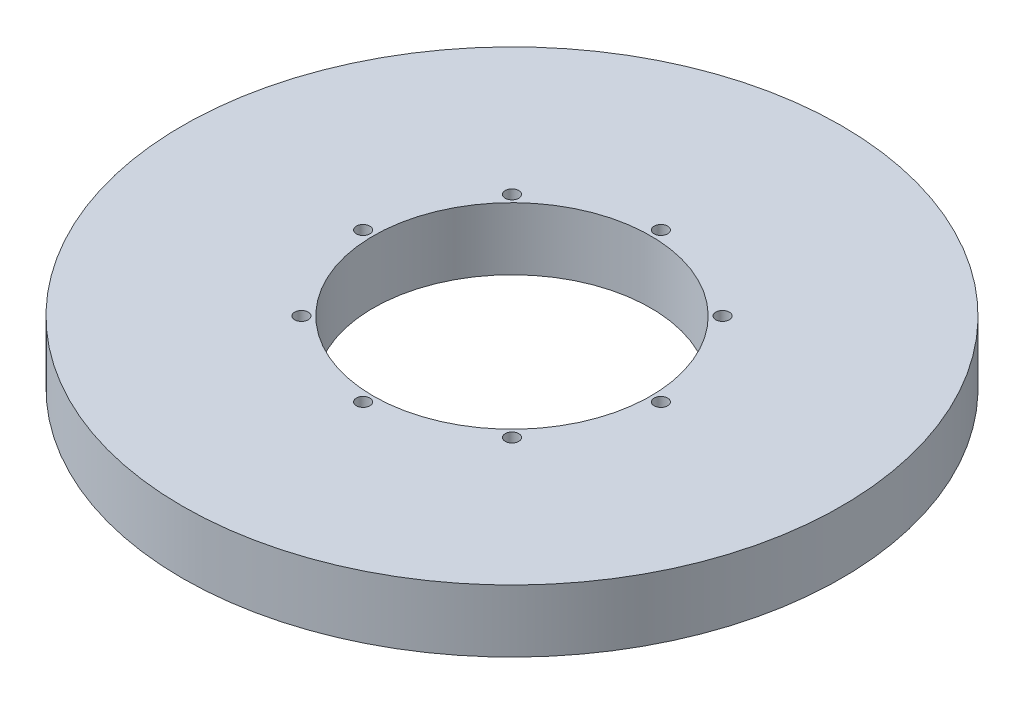
SolidWorks part; units mm, degrees
ref_plane "Front Plane" through (0, 0, 0) normal (0, 0, 1) x (1, 0, 0)
ref_plane "Top Plane" through (0, 0, 0) normal (0, 1, 0) x (1, 0, 0)
ref_plane "Right Plane" through (0, 0, 0) normal (1, 0, 0) x (0, 0, -1)
sketch "Sketch1" plane through (0, 0, 0) normal (0, 1, 0) x (1, 0, 0)
  circle A0 centre (0, 0) radius 95
  dimension "FLANGE_OD" = 190
extrude "Boss-Extrude1" add sketch "Sketch1" along normal blind 18
sketch "Sketch2" plane through (0, 0, 0) normal (0, 1, 0) x (1, 0, 0)
  circle A0 centre (0, 0) radius 40
  dimension "BORE_D" = 80
extrude "Cut-Extrude1" cut sketch "Sketch2" along normal through all
sketch "Sketch3" plane through (0, 18, 0) normal (0, 1, 0) x (1, 0, 0)
  circle A0 centre (0, 0) radius 42.9197 construction
  circle A1 centre (-42.9197, 0) radius 1.9489
  dimension "BOLT_D" = 3.8977
  dimension "BOLT_PCD" = 85.8394
extrude "Cut-Extrude2" cut sketch "Sketch3" against normal blind 12.4713
pattern_circular "CirPattern1" count 8 over 360 about axis through (0, 0, 0) along (0, 1, 0) of "Cut-Extrude2"
